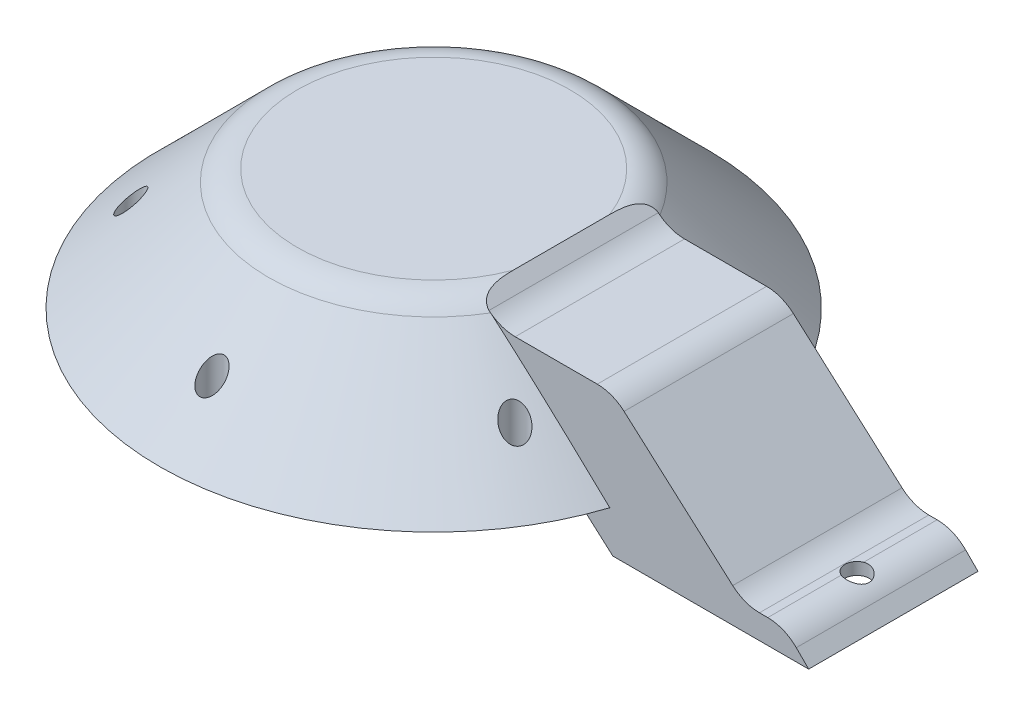
SolidWorks part; units mm, degrees
ref_plane "Front Plane" through (0, 0, 0) normal (0, 0, 1) x (1, 0, 0)
ref_plane "Top Plane" through (0, 0, 0) normal (0, 1, 0) x (1, 0, 0)
ref_plane "Right Plane" through (0, 0, 0) normal (1, 0, 0) x (0, 0, -1)
sketch "Sketch1" plane through (0, 0, 0) normal (0, 0, 1) x (1, 0, 0)
  line L0 (-34, 0) -> (-29, 0)
  line L1 (-29, 0) -> (-19, 10)
  line L2 (-19, 10) -> (0, 10)
  line L3 (-34, 0) -> (-19, 15)
  line L4 (-19, 15) -> (0, 15)
  line L5 (0, 15) -> (0, 10)
  line L6 (0, 30.7889) -> (0, -8.1222) construction
  point P9 (-19.0066, 15)
  dimension "D1" = 34
  dimension "D2" = 5
  dimension "D3" = 10
  dimension "D4" = 45
revolve "Revolve1" add sketch "Sketch1" angle 360 about L6
sketch "Sketch3" plane through (0, 15, 0) normal (0, 1, 0) x (1, 0, 0)
  line L0 (0, 0) -> (15.8351, 0) construction
  line L1 (32.3381, 10.5) -> (15.8351, 10.5)
  line L3 (32.3381, -10.5) -> (15.8351, -10.5)
  line L4 (15.8351, 10.5) -> (15.8351, -10.5)
  line L5 (15.8351, 10.5) -> (15.8351, 0) construction
  line L6 (15.8351, 0) -> (15.8351, -10.5) construction
  circle A0 centre (0, 0) radius 34 construction
  arc A1 (32.3381, -10.5) -> (32.3381, 10.5) centre (0, 0) ccw
  circle A5 centre (0, 0) radius 19 construction
  point P3 (15.8384, -10.4949)
  dimension "D2" = 21
extrude "Cut-Extrude2" cut sketch "Sketch3" against normal through all both and the other way through all
sketch "Sketch18" plane through (0, 0, -10.5) normal (0, 0, 1) x (1, 0, 0)
  line L0 (15.8351, 15) -> (-19, 15) construction
  line L2 (15.8351, 10) -> (15.8351, 15)
  line L7 (15.8351, 15) -> (18.7619, 12.5)
  line L8 (18.7619, 12.5) -> (32.6863, 12.5)
  line L11 (57, -5) -> (54, -2)
  line L12 (15.8351, 10) -> (32.7113, -5)
  line L13 (32.7113, -5) -> (57, -5)
  line L14 (54, -2) -> (49, -2)
  line L15 (49, -2) -> (32.6863, 12.5)
  spline S0 degree 3 poles (15.8351, 10) (17.7583, 8.3971) (19.6383, 6.7459) (23.3606, 3.4012) (25.2017, 1.7065) (27.0324, 0) knots 0 0 0 0 0.5 0.5 1 1 1 1 construction
  spline S1 degree 3 poles (32.3381, 0) (29.6441, 2.5622) (26.9368, 5.1097) (22.8283, 8.8787) (21.4507, 10.1261) (18.6684, 12.5911) (17.264, 13.8091) (15.8351, 15) knots 0 0 0 0 0.5 0.5 0.75 0.75 1 1 1 1 construction
  point P1 (0, 0)
  point P3 (16.1795, 10)
  point P6 (0, 0)
  point P9 (0, 0)
  point P12 (0, 0)
  point P16 (0, 0)
  point P19 (0, 0)
  point P22 (51.8979, -2.56)
  point P23 (0, 0)
  point P24 (50, -5.06)
  point P25 (54.5415, -4.5523)
  point P26 (0, 0)
  point P27 (0, 0)
  point P28 (34.1865, 12.4738)
  point P29 (0, 0)
  point P32 (0, 0)
  point P33 (0, 0)
  point P34 (32.3276, -5)
  point P35 (32.6856, -5)
  point P36 (41.5192, -5)
  point P37 (32.3276, -5)
  point P38 (32.6863, -5)
  dimension "D1" = 54
  dimension "D2" = 45
  dimension "D3" = 5
  dimension "D4" = 20
  dimension "D5" = 2.5
  dimension "D6" = 3
extrude "Boss-Extrude10" add sketch "Sketch18" along normal up to surface (21 mm away) up to face at (22.0969, 6.875, 10.5)
sketch "Sketch2" plane through (0, 15, 0) normal (0, 1, 0) x (1, 0, 0)
  circle A0 centre (0, 0) radius 27.5 construction
  circle A1 centre (0, 27.5) radius 1.5
  circle A2 centre (23.8157, 13.75) radius 1.5
  circle A3 centre (23.8157, -13.75) radius 1.5
  circle A4 centre (0, -27.5) radius 1.5
  circle A5 centre (-23.8157, -13.75) radius 1.5
  circle A6 centre (-23.8157, 13.75) radius 1.5
  circle A7 centre (52.5, 0) radius 1.5
  point P5 (0, 0)
  point P17 (0, 0)
  dimension "D1" = 55
  dimension "D2" = 3
  dimension "D3" = 6
  dimension "D4" = 52.5
extrude "Cut-Extrude1" cut sketch "Sketch2" against normal through all both and the other way through all
sketch "Sketch20" plane through (0, 0, 10.5) normal (0, 0, 1) x (1, 0, 0)
  line L0 (53.3787, -3.5) -> (55.3586, -5.4799)
  line L1 (53.3787, -3.5) -> (48.4297, -3.5)
  line L2 (48.4297, -3.5) -> (32.116, 11)
  line L8 (18.7619, 12.5) -> (18.7511, 12.5093)
  line L9 (55.3586, -5.4799) -> (32.4987, -5.4799)
  line L10 (32.3381, 0) -> (27.0859, 0)
  line L11 (32.7113, -5) -> (57, -5)
  line L12 (57, -5) -> (54, -2)
  line L13 (54, -2) -> (49, -2)
  line L14 (49, -2) -> (32.6863, 12.5)
  line L15 (32.6863, 12.5) -> (18.7619, 12.5)
  line L16 (18.7619, 12.5) -> (18.7511, 12.5093) construction
  line L20 (57, -5) -> (54, -2) construction
  line L21 (54, -2) -> (49, -2) construction
  line L22 (49, -2) -> (32.6863, 12.5) construction
  line L23 (32.6863, 12.5) -> (18.7619, 12.5) construction
  line L24 (55.9393, -6.0607) -> (53.3787, -3.5) construction
  line L25 (32.4987, -5.4799) -> (13.9574, 11)
  line L26 (13.9574, 11) -> (32.116, 11)
  line L28 (27.0859, 0) -> (32.7113, -5) construction
  line L33 (27.0859, 0) -> (32.7113, -5)
  line L35 (32.116, 11) -> (18.7619, 11) construction
  spline S2 degree 3 poles (-821.8442, -529.1542) (-119.755, 110.9877) (-39.7098, 66.7576) (122.1755, -83.0251) (184.2084, -210.3696) (938.1975, 423.5752) knots -13.954518 -13.954518 -13.954518 -13.954518 0.5 0.5 21.870322 21.870322 21.870322 21.870322 only from (18.7511, 12.5093) to (32.3381, 0)
  point P14 (32.3198, -5.3209)
  dimension "D3" = 0.5
  dimension "D1" = 0
  dimension "D2" = 1.5
extrude "Cut-Extrude8" cut sketch "Sketch20" against normal offset from surface (18 mm away) 1.5 from offset 1.5 up to face at (36.5698, 1.9172, -10.5) offset against normal yes
fillet "Fillet10" radius 5 4 edges at (48.4297, -3.5, 0) (32.6863, 12.5, 0) (18.7619, 12.5, 0) (-19, 15, 0)
fillet "Fillet11" radius 5 2 edges at (54, -2, -5.25) (49, -2, 0)
